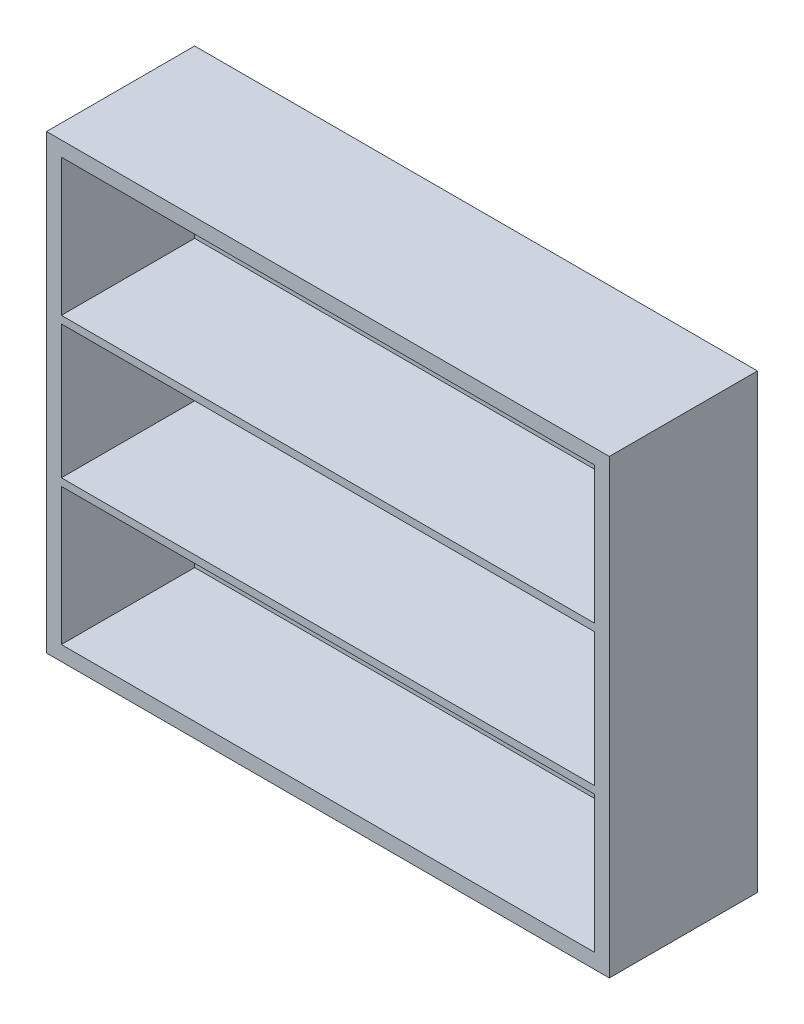
SolidWorks part; units mm, degrees
ref_plane "Plan de face" through (0, 0, 0) normal (0, 0, 1) x (1, 0, 0)
ref_plane "Plan de dessus" through (0, 0, 0) normal (0, 1, 0) x (1, 0, 0)
ref_plane "Plan de droite" through (0, 0, 0) normal (1, 0, 0) x (0, 0, -1)
sketch "Esquisse1" plane through (0, 0, 0) normal (0, 0, 1) x (1, 0, 0)
  line L1 (0, 0) -> (76, 0)
  line L2 (0, 0) -> (0, 61)
  line L3 (0, 61) -> (76, 61)
  line L4 (76, 0) -> (76, 61)
  dimension "D1" = 76
  dimension "D2" = 61
extrude "Boss.-Extru.1" add sketch "Esquisse1" against normal blind 20
sketch "Esquisse2" plane through (0, 0, 0) normal (0, 0, 1) x (1, 0, 0)
  line L0 (76, 0) -> (76, 61) construction
  line L1 (0, 0) -> (76, 0) construction
  line L2 (0, 61) -> (0, 0) construction
  line L3 (76, 61) -> (0, 61) construction
  line L4 (76, 0) -> (76, 61)
  line L5 (0, 0) -> (76, 0)
  line L6 (0, 61) -> (0, 0)
  line L7 (76, 61) -> (0, 61)
  line L8 (74, 2) -> (74, 20.5)
  line L9 (74, 59) -> (2, 59)
  line L10 (2, 59) -> (2, 40.5)
  line L11 (2, 2) -> (74, 2)
  line L12 (2, 20.5) -> (2, 2)
  line L14 (2, 39.5) -> (2, 21.5)
  line L16 (74, 39.5) -> (74, 21.5)
  line L17 (74, 40.5) -> (74, 59)
  line L18 (2, 59) -> (2, 2) construction
  line L19 (2, 20.5) -> (74, 20.5)
  line L20 (74, 2) -> (74, 59) construction
  line L21 (2, 39.5) -> (74, 39.5)
  line L22 (2, 21.5) -> (74, 21.5)
  line L23 (2, 40.5) -> (74, 40.5)
  dimension "D1" = 2
extrude "Enlèv. mat.-Extru.1" cut sketch "Esquisse2" against normal blind 18 contours L8 L19 L12 L11 | L14 L22 L16 L21 | L9 L10 L23 L17
sketch "Esquisse3" plane through (0, 0, -18) normal (0, 0, 1) x (1, 0, 0)
  line L0 (2, 49.75) -> (74, 49.75) construction
  line L1 (2, 59) -> (2, 40.5) construction
  line L2 (74, 40.5) -> (74, 59) construction
  line L3 (2, 30.5) -> (74, 30.5) construction
  line L4 (2, 39.5) -> (2, 21.5) construction
  line L5 (74, 39.5) -> (74, 21.5) construction
  circle A0 centre (38, 49.75) radius 2
  circle A1 centre (38, 11.25) radius 2
  dimension "D1" = 4
extrude "Enlèv. mat.-Extru.2" cut sketch "Esquisse3" against normal up to next
